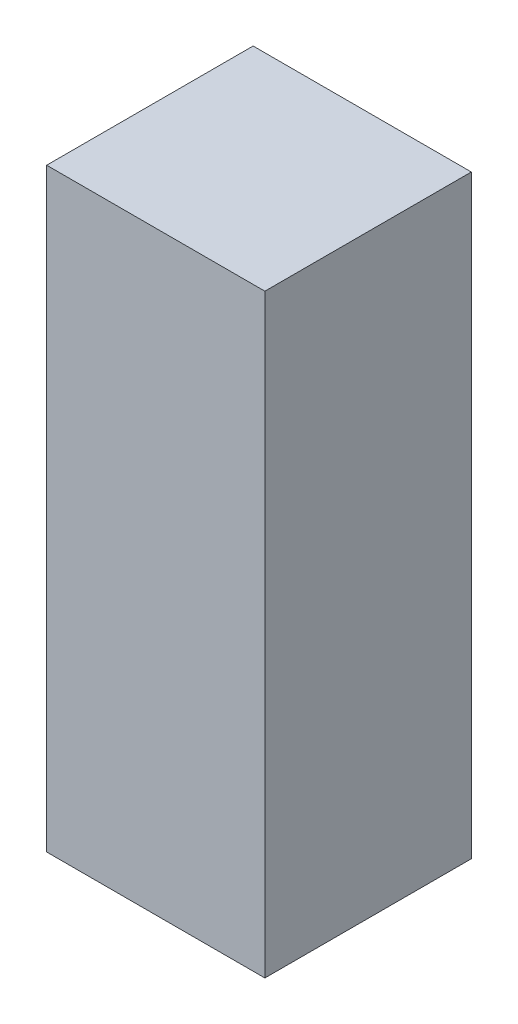
SolidWorks part; units mm, degrees
material "K110"
ref_plane "Front Plane" through (0, 0, 0) normal (0, 0, 1) x (1, 0, 0)
ref_plane "Top Plane" through (0, 0, 0) normal (0, 1, 0) x (1, 0, 0)
ref_plane "Right Plane" through (0, 0, 0) normal (1, 0, 0) x (0, 0, -1)
sketch "Sketch1" plane through (0, 0, 0) normal (0, 1, 0) x (1, 0, 0)
  line L1 (-10.125, -9.58) -> (10.125, -9.58)
  line L2 (-10.125, -9.58) -> (-10.125, 9.58)
  line L3 (-10.125, 9.58) -> (10.125, 9.58)
  line L4 (10.125, -9.58) -> (10.125, 9.58)
  line L5 (-10.125, -9.58) -> (10.125, 9.58) construction
  line L6 (-10.125, 9.58) -> (10.125, -9.58) construction
  point P0 (0, 0)
  dimension "D1" = 19.16
  dimension "D2" = 20.25
extrude "Boss-Extrude1" add sketch "Sketch1" against normal blind 55.2
